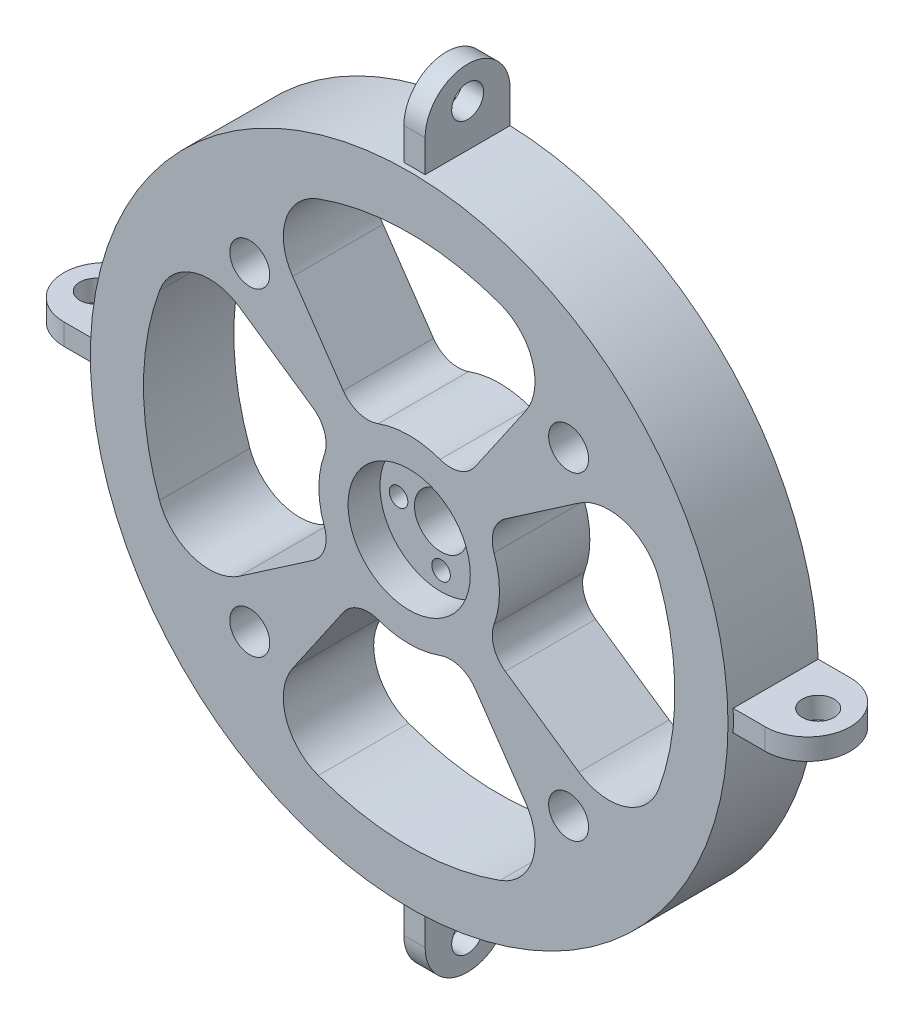
SolidWorks part; units mm, degrees
material "ABS"
ref_plane "前视基准面" through (0, 0, 0) normal (0, 0, 1) x (1, 0, 0)
ref_plane "上视基准面" through (0, 0, 0) normal (0, 1, 0) x (1, 0, 0)
ref_plane "右视基准面" through (0, 0, 0) normal (1, 0, 0) x (0, 0, -1)
sketch "草图1" plane through (0, 0, 0) normal (0, 0, 1) x (1, 0, 0)
  circle A0 centre (0, 0) radius 60
  dimension "D1" = 120
extrude "凸台-拉伸1" add sketch "草图1" along normal blind 17
sketch "草图2" plane through (0, 0, 17) normal (0, 0, 1) x (1, 0, 0)
  line L0 (0, 30) -> (0, 0) construction
  line L1 (0, 0) -> (0, -30) construction
  line L2 (-30, 0) -> (0, 0) construction
  line L3 (0, 0) -> (30, 0) construction
  circle A4 centre (-30, 30) radius 3.76
  circle A5 centre (30, 30) radius 3.76
  circle A6 centre (30, -30) radius 3.76
  circle A7 centre (-30, -30) radius 3.76
  dimension "D1" = 7.52
  dimension "D2" = 7.52
  dimension "D7" = 7.52
  dimension "D8" = 7.52
  dimension "D3" = 30
  dimension "D4" = 30
  dimension "D5" = 30
  dimension "D6" = 30
  dimension "D9" = 60
  dimension "D10" = 60
extrude "切除-拉伸1" cut sketch "草图2" against normal through all
sketch "草图3" plane through (0, 0, 0) normal (1, 0, 0) x (0, 0, -1)
  line L0 (0, 58) -> (-16, 58)
  line L1 (-16, 58) -> (-16, 66)
  line L2 (0, 66) -> (0, 58)
  line L3 (0, 0) -> (-35.6052, 0) construction
  arc A0 (-16, 66) -> (0, 66) centre (-8, 66) cw
  dimension "D3" = 8
  dimension "D1" = 58
  dimension "D2" = 8
  dimension "D4" = 0
extrude "凸台-拉伸2" add sketch "草图3" along normal blind 2 and the other way blind 2
sketch "草图4" plane through (2, 0, 0) normal (1, 0, 0) x (0, 0, -1)
  line L0 (-16, 59.9667) -> (0, 59.9667) construction
  line L1 (0, 59.9667) -> (0, 66) construction
  circle A0 centre (-8, 67.9667) radius 3
  dimension "D1" = 6
  dimension "D2" = 8
  dimension "D3" = 8
extrude "切除-拉伸7" cut sketch "草图4" against normal through all
sketch "草图5" plane through (0, 0, 0) normal (0, 0, -1) x (-1, 0, 0)
  circle A0 centre (0, 0) radius 5
  dimension "D1" = 10
extrude "切除-拉伸3" cut sketch "草图5" against normal up to next
sketch "草图6" plane through (0, 0, 17) normal (0, 0, 1) x (1, 0, 0)
  circle A0 centre (0, 0) radius 11.5
  dimension "D1" = 23
extrude "切除-拉伸4" cut sketch "草图6" against normal blind 6
sketch "草图7" plane through (0, 0, 11) normal (0, 0, 1) x (1, 0, 0)
  circle A0 centre (0, 0) radius 8 construction
  circle A1 centre (-8, 0) radius 1.75
  circle A2 centre (0, 8) radius 1.75
  circle A3 centre (8, 0) radius 1.75
  circle A4 centre (0, -8) radius 1.75
  dimension "D1" = 16
  dimension "D2" = 3.5
  dimension "D3" = 3.5
  dimension "D4" = 3.5
  dimension "D5" = 3.5
extrude "切除-拉伸5" cut sketch "草图7" against normal up to next
sketch "草图8" plane through (0, 0, 17) normal (0, 0, 1) x (1, 0, 0)
  line L0 (-37.5877, -13.6808) -> (0, 0) construction
  line L1 (0, 0) -> (-37.5877, 13.6808) construction
  line L2 (0, 0) -> (-30, 0) construction
  line L3 (-37.5877, -13.6808) -> (-46.9846, -17.101) construction
  line L4 (-37.5877, 13.6808) -> (-46.9846, 17.101) construction
  line L13 (-18.0919, -12.4238) -> (0, 0) construction
  line L14 (-18.0919, 12.4238) -> (-31.9269, 21.9243)
  line L15 (-31.9269, -21.9243) -> (-18.0919, -12.4238)
  arc A0 (-37.5877, -13.6808) -> (-37.5877, 13.6808) centre (0, 0) cw construction
  arc A6 (-46.9846, -17.101) -> (-46.9846, 17.101) centre (0, 0) cw
  arc A7 (-46.9846, -17.101) -> (-31.9269, -21.9243) centre (-37.5877, -13.6808) ccw
  arc A9 (-15.9748, -5.8143) -> (-15.9748, 5.8143) centre (0, 0) cw
  arc A11 (-15.9748, -5.8143) -> (-18.0919, -12.4238) centre (-21.2997, -7.7525) cw
  arc A31 (-15.9748, 5.8143) -> (-18.0919, 12.4238) centre (-21.2997, 7.7525) ccw
  arc A32 (-46.9846, 17.101) -> (-31.9269, 21.9243) centre (-37.5877, 13.6808) cw
  dimension "D2" = 20
  dimension "D3" = 40
  dimension "D4" = 50
  dimension "D5" = 17
extrude "切除-拉伸6" cut sketch "草图8" against normal up to next
pattern_circular "阵列(圆周)3" count 4 over 360 about axis through (0, 0, 17) along (0, 0, 1) of "切除-拉伸6"
pattern_circular "阵列(圆周)4" count 4 over 360 about axis through (0, 0, 17) along (0, 0, 1) of "凸台-拉伸2", "切除-拉伸7"
